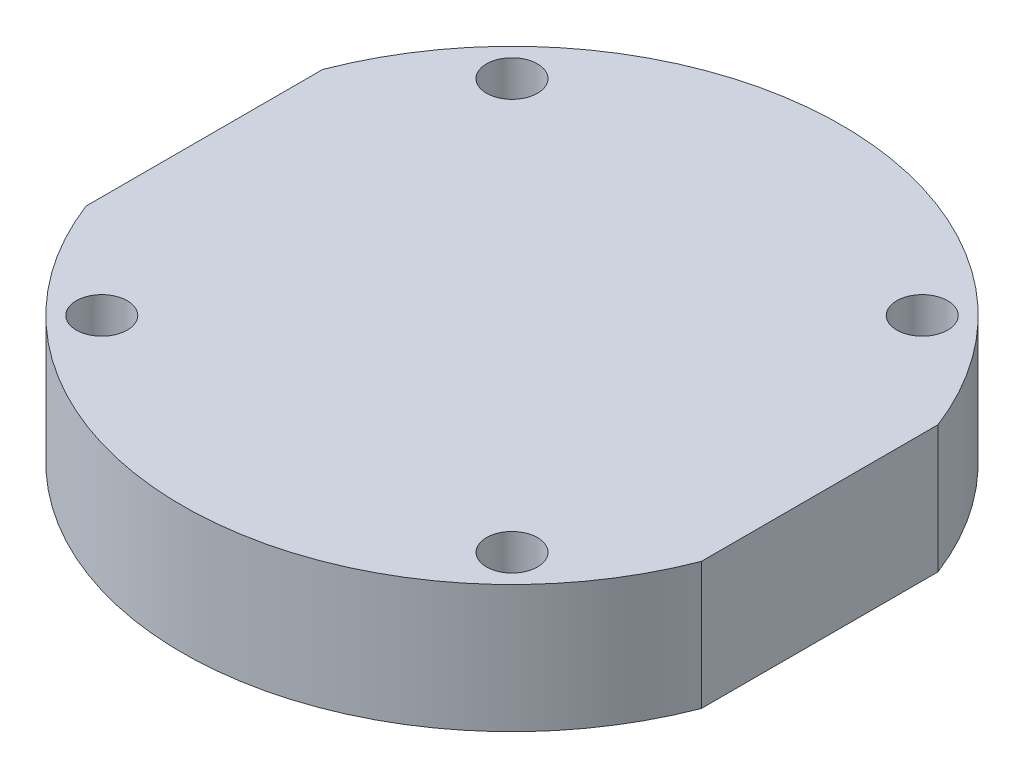
SolidWorks part; units mm, degrees
material "Copper"
ref_plane "Front Plane" through (0, 0, 0) normal (0, 0, 1) x (1, 0, 0)
ref_plane "Top Plane" through (0, 0, 0) normal (0, 1, 0) x (1, 0, 0)
ref_plane "Right Plane" through (0, 0, 0) normal (1, 0, 0) x (0, 0, -1)
ref_axis "Y Axis" through (0, 6.6675, 0) along (0, -1, 0)
sketch "outer" plane through (0, 0, 0) normal (0, 1, 0) x (1, 0, 0)
  circle A0 centre (0, 0) radius 19.05
  dimension "D1" = 38.1
extrude "Body" add sketch "outer" along normal blind 7.366
sketch "inner" plane through (0, 0, 0) normal (0, 1, 0) x (1, 0, 0)
  circle A0 centre (0, 0) radius 11.938
  dimension "D1" = 23.876
extrude "Pocket" cut sketch "inner" along normal blind 4.826
sketch "Screw Position" plane through (0, 0, 0) normal (0, 1, 0) x (1, 0, 0)
  point P0 (-11.8539, 11.8539)
  dimension "D1" = 16.764
hole_wizard "#4 Clearance Hole1" positions "Sketch7" profile "Sketch8" hole size "#4" standard "ANSI Inch" end condition through all
sketch "Sketch7" plane through (0, 7.366, 0) normal (0, 1, 0) x (1, 0, 0)
  point P0 (-11.8539, 11.8539)
sketch "Sketch8" plane through (-11.8539, 7.366, -11.8539) normal (1, 0, 0) x (0, 0, 1)
  line L0 (0, 0) -> (0, 7.366)
  line L1 (0, 7.366) -> (1.4732, 7.366)
  line L2 (1.4732, 7.366) -> (1.4732, 0)
  line L5 (1.4732, 0) -> (0, 0)
  line L11 (0, -6.35) -> (0, 107.95) construction
  dimension "Thru Hole Dia." = 2.9464
  dimension "Thru Hole Depth" = 7.366
pattern_circular "Screw Holes" count 4 over 360 about axis through (0, 6.6675, 0) along (0, -1, 0) of "#4 Clearance Hole1"
sketch "Post Sketch" plane through (0, 0, 0) normal (0, 1, 0) x (1, 0, 0)
  circle A0 centre (0, -5.334) radius 1
  circle A1 centre (5.334, -5.334) radius 1
  point P0 (0, -5.334)
  point P1 (5.334, -5.334)
  dimension "D3" = 2
  dimension "D4" = 2
  dimension "D1" = 5.334
extrude "Post" add sketch "Post Sketch" against normal blind 4.826 from surface starting at face at (0, 4.826, 11.938)
pattern_circular "CirPattern1" count 4 over 360 about axis through (0, 6.6675, 0) along (0, -1, 0) of "Post"
sketch "Flat Cut Sketch" plane through (0, 0, 0) normal (0, 1, 0) x (1, 0, 0)
  line L0 (0, 19.05) -> (0, -19.05) construction
  line L1 (-17.78, 19.05) -> (-20.32, -19.05) construction
  line L2 (17.78, -19.05) -> (20.32, -19.05)
  line L3 (17.78, -19.05) -> (17.78, 19.05)
  line L4 (17.78, 19.05) -> (20.32, 19.05)
  line L5 (20.32, -19.05) -> (20.32, 19.05)
  line L6 (17.78, -19.05) -> (20.32, 19.05) construction
  line L7 (17.78, 19.05) -> (20.32, -19.05) construction
  line L8 (-17.78, -19.05) -> (-20.32, 19.05) construction
  line L9 (-20.32, -19.05) -> (-20.32, 19.05)
  line L10 (-17.78, 19.05) -> (-20.32, 19.05)
  line L11 (-17.78, -19.05) -> (-17.78, 19.05)
  line L12 (-17.78, -19.05) -> (-20.32, -19.05)
  circle A0 centre (0, 0) radius 19.05 construction
  point P5 (19.05, 0)
  point P14 (-19.05, 0)
  dimension "D1" = 38.1
  dimension "D2" = 2.54
extrude "Flat Cut" cut sketch "Flat Cut Sketch" along normal through all
equation "\"outer_d\"= 3 / 2in"
equation "\"top_h\"= 1 / 4in"
equation "\"screw_r\"= 0.66in"
equation "\"inner_d\"= 0.94in"
equation "\"inner_h\"= 150mil"
equation "\"D1@outer\" = \"outer_d\""
equation "\"D1@Body\"=\"top_h\" + \"inset_h\""
equation "\"D1@inner\"=\"inner_d\""
equation "\"D1@Pocket\"=\"inner_h\" + \"inset_h\""
equation "\"D1@Screw Position\"=\"screw_r\""
equation "\"post_r1\"= 0.21in"
equation "\"post_r2\"= \"post_r1\" * sqr ( 2 )"
equation "\"post_bottom_h\"= 0.04in"
equation "\"D1@Post Sketch\" = \"post_r1\""
equation "\"D2@Post Sketch\" = \"post_r2\""
equation "\"post_d\"= 2mm"
equation "\"D3@Post Sketch\"=\"post_d\""
equation "\"D4@Post Sketch\"=\"post_d\""
equation "\"D1@Post\" = \"inner_h\" + \"post_bottom_h\""
equation "\"inset_h\"= 0.04in"
equation "\"D1@Flat Cut Sketch\" = \"outer_d\""
equation "\"flat_cut\"= 0.05in"
equation "\"D2@Flat Cut Sketch\" = \"flat_cut\" * 2"
